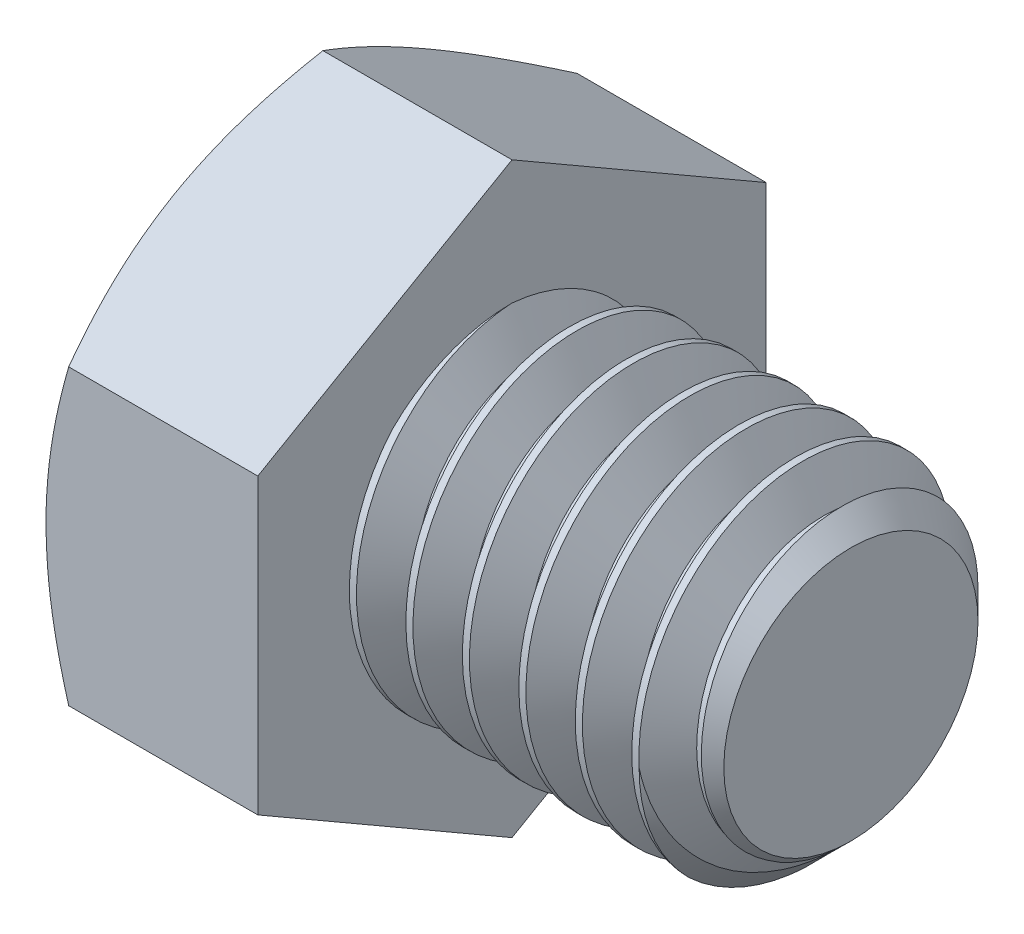
SolidWorks part; units mm, degrees
ref_plane "Front Plane" through (0, 0, 0) normal (0, 0, 1) x (1, 0, 0)
ref_plane "Top Plane" through (0, 0, 0) normal (0, 1, 0) x (1, 0, 0)
ref_plane "Right Plane" through (0, 0, 0) normal (1, 0, 0) x (0, 0, -1)
sketch "Sketch1" plane through (0, 0, 0) normal (0, 0, 1) x (1, 0, 0)
  line L0 (-7.7391, 0) -> (7.7391, 0) construction
  line L1 (7.7391, 4.7625) -> (7.7391, -4.7625) construction
  line L2 (-1.7859, 7.1438) -> (-1.7859, -7.1438) construction
  line L3 (-7.7391, 7.1437) -> (-7.7391, -7.1437) construction
  point P9 (-1.7859, 0)
  point P10 (2.1828, -4.7625)
  dimension "D1" = 5.5562
  dimension "Screw Dia" = 9.525
  dimension "Hex" = 14.2875
  dimension "Head Ht" = 5.9531
  dimension "Screw Lenght" = 9.525
ref_plane "Plane2" through (7.7391, 0, 0) normal (1, 0, 0) x (0, 0, -1)
sketch "Sketch5" plane through (7.7391, 0, 0) normal (1, 0, 0) x (0, 0, -1)
  circle A0 centre (0, 0) radius 4.7625
extrude "Boss-Extrude3" add sketch "Sketch5" against normal up to vertex (9.525 mm away) up to point (-1.7859, 0, 0)
sketch "Sketch9" plane through (7.7391, 0, 0) normal (1, 0, 0) x (0, 0, -1)
  circle A1 centre (0, 0) radius 4.7625
  circle A2 centre (0, 0) radius 4.7625
  dimension "D1" = 0
curve "Helix/Spiral1" pitch 1.5875 height 11.1125 turns 7 parameters "Pitch"=1.5875
chamfer "Chamfer1" distance 1.1906 angle 45 1 edges at (7.7391, 0, -4.7625)
sketch "Sketch10" plane through (0, 0, 0) normal (0, 0, 1) x (1, 0, 0)
  line L0 (7.7391, 4.7625) -> (8.3344, 3.7314)
  line L1 (8.3344, 3.7314) -> (8.5328, 3.7314)
  line L2 (8.5328, 3.7314) -> (9.1281, 4.7625)
  line L3 (7.7391, 4.7625) -> (9.1281, 4.7625)
  line L4 (8.4336, 4.7625) -> (8.4336, 3.7314) construction
  line L5 (8.0367, 4.2469) -> (8.8305, 4.2469) construction
  dimension "D1" = 60
  dimension "D2" = 0.1984
  dimension "D3" = 0.7937
sweep "Cut-Sweep1" cut profiles "Sketch10" path "Helix/Spiral1"
sketch "Sketch6" plane through (-1.7859, 0, 0) normal (-1, 0, 0) x (0, 0, 1)
  line L0 (0, 7.1438) -> (0, -7.1438) construction
  line L1 (7.1437, 4.1244) -> (0, 8.2489)
  line L2 (0, 8.2489) -> (-7.1438, 4.1244)
  line L3 (-7.1438, 4.1244) -> (-7.1437, -4.1244)
  line L4 (-7.1437, -4.1244) -> (0, -8.2489)
  line L5 (0, -8.2489) -> (7.1438, -4.1244)
  line L6 (7.1438, -4.1244) -> (7.1437, 4.1244)
  circle A0 centre (0, 0) radius 7.1438 construction
extrude "Boss-Extrude4" add sketch "Sketch6" along normal up to vertex (5.9531 mm away) up to point (-7.7391, -7.1437, 0)
sketch "Sketch7" plane through (-7.7391, 0, 0) normal (-1, 0, 0) x (0, 0, 1)
  circle A0 centre (0, 0) radius 7.1438 construction
  circle A1 centre (0, 0) radius 7.1438
sketch "Sketch8" plane through (-7.7391, 0, 0) normal (-1, 0, 0) x (0, 0, 1)
  circle A0 centre (0, 0) radius 7.1438 construction
  circle A1 centre (0, 0) radius 7.1438
extrude "Cut-Extrude3" cut sketch "Sketch8" against normal through all draft 60 flip side to cut
equation "\"D2@Sketch10\" = \"Pitch@Helix/Spiral1\"*.125"
equation "\"D3@Sketch10\" = \"Pitch@Helix/Spiral1\"*.5"
equation "\"D3@Helix/Spiral1\" = \"Screw Lenght@Sketch1\"+\"Pitch@Helix/Spiral1\""
equation "\"D1@Chamfer1\" = \"Pitch@Helix/Spiral1\"*.75"
equation "\"D1@Sketch1\" = \"Pitch@Helix/Spiral1\"*3.5"
